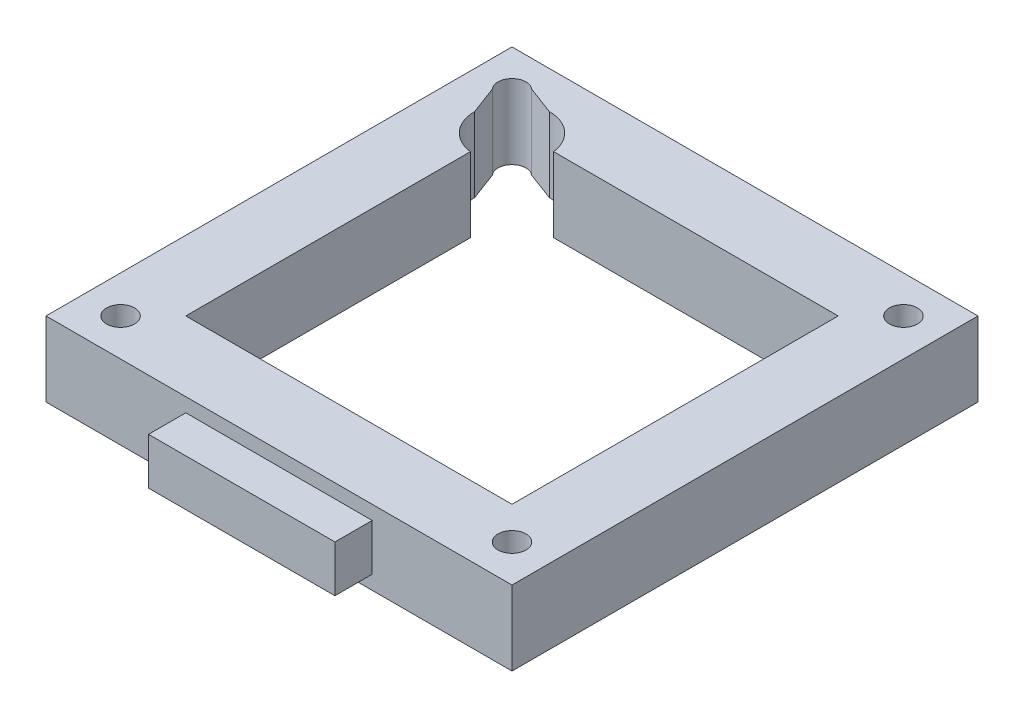
SolidWorks part; units mm, degrees
ref_plane "Front Plane" through (0, 0, 0) normal (0, 0, 1) x (1, 0, 0)
ref_plane "Top Plane" through (0, 0, 0) normal (0, 1, 0) x (1, 0, 0)
ref_plane "Right Plane" through (0, 0, 0) normal (1, 0, 0) x (0, 0, -1)
sketch "Sketch1" plane through (0, 0, 0) normal (0, 1, 0) x (1, 0, 0)
  line L0 (17.5, 17.5) -> (-13.0314, 17.5)
  line L1 (-25, -25) -> (25, -25)
  line L2 (-25, -25) -> (-25, 25)
  line L3 (-25, 25) -> (25, 25)
  line L4 (25, -25) -> (25, 25)
  line L5 (0, 25) -> (0, -25) construction
  line L6 (-25, 0) -> (25, 0) construction
  line L11 (0, 20) -> (0, -20) construction
  line L12 (-20, 0) -> (20, 0) construction
  line L13 (-17.5, -17.5) -> (17.5, -17.5)
  line L16 (17.5, -17.5) -> (17.5, 17.5)
  line L17 (0, 17.5) -> (0, -17.5) construction
  line L18 (-17.5, 0) -> (17.5, 0) construction
  line L19 (-17.5, -17.5) -> (-17.5, 13.0314)
  line L20 (-22.1301, 20.0137) -> (-21, 17)
  line L21 (-20.0137, 22.1301) -> (-17, 21)
  arc A0 (-20.0137, 22.1301) -> (-22.1301, 20.0137) centre (-21, 21) ccw
  circle A1 centre (21, 21) radius 1.5
  circle A2 centre (21, -21) radius 1.5
  circle A3 centre (-21, -21) radius 1.5
  arc A4 (-21, 17) -> (-17, 21) centre (-17, 17) ccw
  point P0 (0, 0)
  point P4 (0, 0)
  point P13 (0, 0)
  dimension "D1" = 50
  dimension "D2" = 50
  dimension "D4" = 35
extrude "Support" add sketch "Sketch1" along normal blind 8 contours L1 L4 L3 L2 A4 L0 L16 L13 L19 L20 A0 L21 A1 A2 A3 region at (-24.2929, 0, 0)
sketch "Sketch2" plane through (0, 0, 0) normal (0, 0, 1) x (1, 0, 0)
  line L4 (-10, 1.5) -> (10, 1.5)
  line L5 (-10, 1.5) -> (-10, 6.5)
  line L6 (-10, 6.5) -> (10, 6.5)
  line L7 (10, 1.5) -> (10, 6.5)
  line L8 (0, 6.5) -> (0, 1.5) construction
  line L9 (-10, 4) -> (10, 4) construction
  point P6 (0, 4)
  dimension "D1" = 20
  dimension "D2" = 5
sketch "Sketch3" plane through (0, 0, 0) normal (1, 0, 0) x (0, 0, -1)
  line L4 (-10, 1.5) -> (10, 1.5)
  line L5 (-10, 1.5) -> (-10, 6.5)
  line L6 (-10, 6.5) -> (10, 6.5)
  line L7 (10, 1.5) -> (10, 6.5)
  line L8 (0, 6.5) -> (0, 1.5) construction
  line L9 (-10, 4) -> (10, 4) construction
  point P6 (0, 4)
  dimension "D1" = 20
  dimension "D2" = 5
extrude "North Cut" cut sketch "Sketch2" along normal blind 4 from surface starting at face at (0, 4, -25)
extrude "South Dowel" add sketch "Sketch2<2>" along normal blind 4 from surface starting at face at (0, 4, 25)
sketch "Sketch2<2>" plane through (0, 0, 0) normal (0, 0, 1) x (1, 0, 0) same geometry as "Sketch2"
extrude "West Cut" cut sketch "Sketch3" along normal blind 4 from surface starting at face at (-25, 4, 0)
